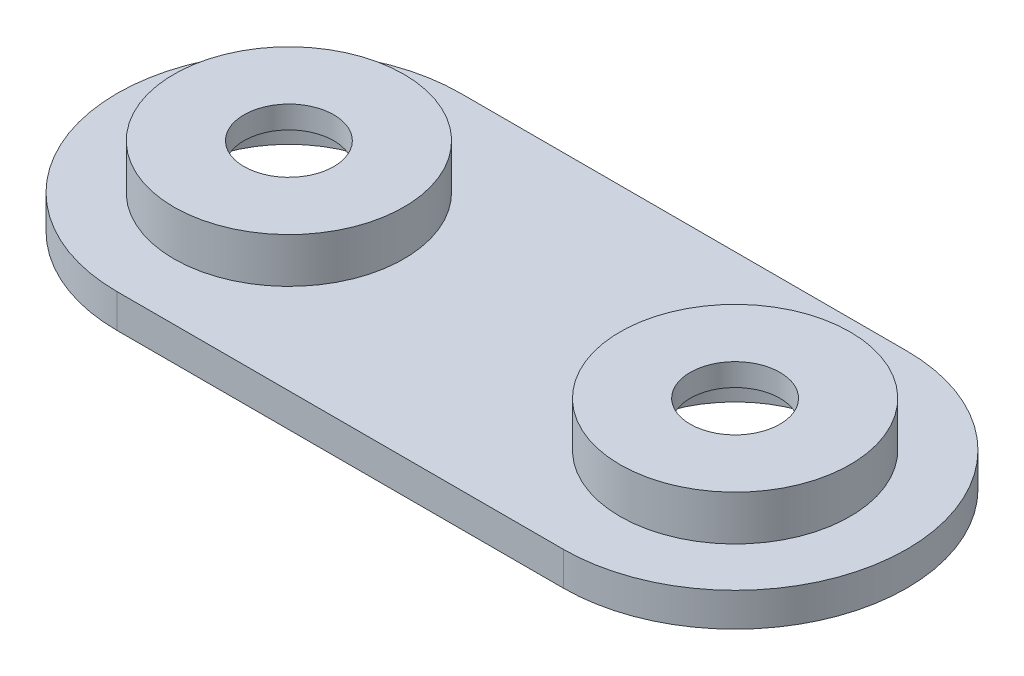
SolidWorks part; units mm, degrees
ref_plane "Front Plane" through (0, 0, 0) normal (0, 0, 1) x (1, 0, 0)
ref_plane "Top Plane" through (0, 0, 0) normal (0, 1, 0) x (1, 0, 0)
ref_plane "Right Plane" through (0, 0, 0) normal (1, 0, 0) x (0, 0, -1)
sketch "Sketch1" plane through (0, 0, 0) normal (0, 1, 0) x (1, 0, 0)
  line L0 (19.8792, 0) -> (-19.8792, 0)
  line L1 (-19.8792, -30.6106) -> (19.8792, -30.6106)
  arc A0 (-19.8792, 0) -> (-19.8792, -30.6106) centre (-19.8792, -15.3053) ccw
  arc A1 (19.8792, -30.6106) -> (19.8792, 0) centre (19.8792, -15.3053) ccw
  point P4 (0, 0)
  dimension "D1" = 39.7583
  dimension "D2" = 30.6106
extrude "Boss-Extrude1" add sketch "Sketch1" along normal blind 3
sketch "Sketch2" plane through (0, 3, 0) normal (0, 1, 0) x (1, 0, 0)
  line L0 (-19.8792, 0) -> (-19.8792, -30.6106) construction
  line L1 (0, 0) -> (0, -30.6106) construction
  line L2 (-19.8792, -30.6106) -> (19.8792, -30.6106) construction
  circle A0 centre (-19.8792, -15.3053) radius 9.5
  circle A2 centre (19.8792, -15.3053) radius 9.5
  dimension "D1" = 19
extrude "Cut-Extrude1" cut sketch "Sketch2" against normal through all
sketch "Sketch3" plane through (0, 3, 0) normal (0, 1, 0) x (1, 0, 0)
  circle A0 centre (19.8792, -15.3053) radius 9.5 construction
  circle A1 centre (19.8792, -15.3053) radius 9.5
  circle A2 centre (-19.8792, -15.3053) radius 9.5 construction
  circle A3 centre (-19.8792, -15.3053) radius 9.5
  circle A4 centre (19.8792, -15.3053) radius 10.25
  circle A5 centre (-19.8792, -15.3053) radius 10.25
  dimension "D1" = 20.5
extrude "Boss-Extrude2" add sketch "Sketch3" along normal blind 2
sketch "Sketch4" plane through (0, 5, 0) normal (0, 1, 0) x (1, 0, 0)
  circle A0 centre (19.8792, -15.3053) radius 10.25 construction
  circle A1 centre (19.8792, -15.3053) radius 10.25
  circle A2 centre (-19.8792, -15.3053) radius 10.25 construction
  circle A3 centre (-19.8792, -15.3053) radius 10.25
extrude "Boss-Extrude3" add sketch "Sketch4" along normal blind 2
sketch "Sketch5" plane through (0, 7, 0) normal (0, 1, 0) x (1, 0, 0)
  circle A0 centre (19.8792, -15.3053) radius 4
  circle A1 centre (-19.8792, -15.3053) radius 4
  dimension "D1" = 8
extrude "Cut-Extrude2" cut sketch "Sketch5" against normal blind 2
